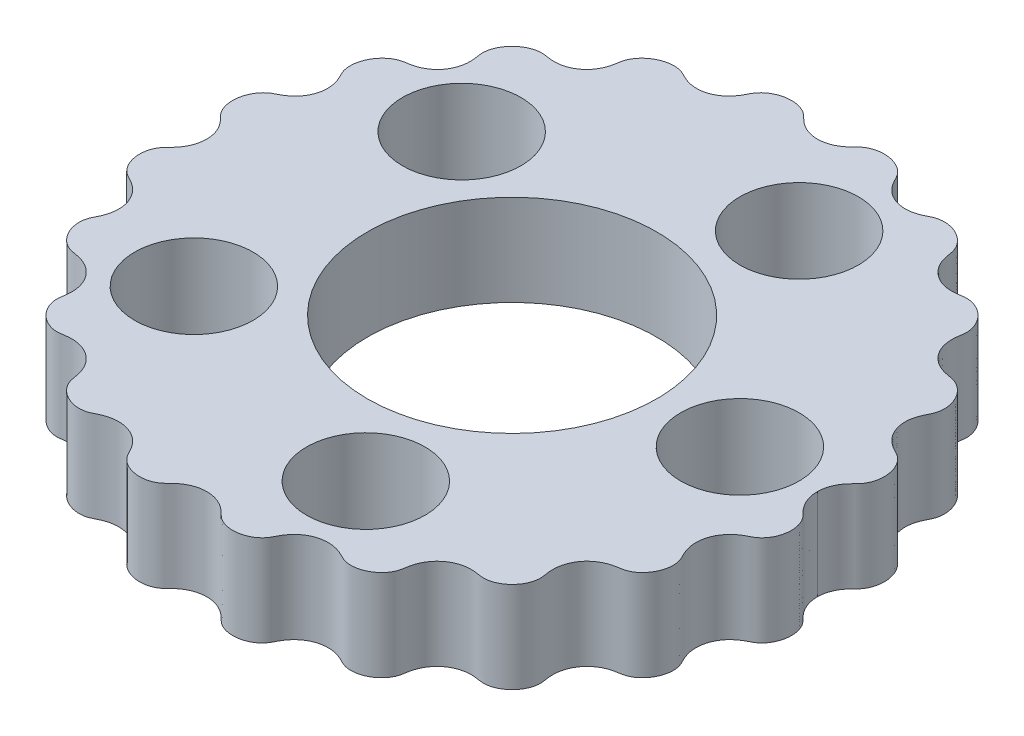
SolidWorks part; units mm, degrees
ref_plane "Front Plane" through (0, 0, 0) normal (0, 0, 1) x (1, 0, 0)
ref_plane "Top Plane" through (0, 0, 0) normal (0, 1, 0) x (1, 0, 0)
ref_plane "Right Plane" through (0, 0, 0) normal (1, 0, 0) x (0, 0, -1)
sketch "MAIN" plane through (0, 0, 0) normal (0, 1, 0) x (1, 0, 0)
  line L0 (-20.1, 0) -> (20.1, 0) construction
  line L1 (0, 0) -> (-0.8, 0)
  line L4 (0, -20.1) -> (0, 20.1) construction
  line L5 (-0.8, -20.2489) -> (-0.8, 20.2572) construction
  circle A22 centre (0, 0) radius 15
  circle A23 centre (15, 0) radius 3.9
  circle A24 centre (4.6353, -14.2658) radius 3.9
  circle A25 centre (-12.1353, -8.8168) radius 3.9
  circle A26 centre (-12.1353, 8.8168) radius 3.9
  circle A27 centre (4.6353, 14.2658) radius 3.9
  circle A29 centre (0, 0) radius 9.525
  spline S0 degree 4 poles (20.5886, 4.7068) (20.68, 4.6551) (20.8532, 4.5348) (21.1393, 4.2364) (21.3748, 3.7649) (21.4816, 3.2447) (21.4517, 2.7569) (21.3623, 2.4139) (21.2306, 2.1338) (21.0766, 1.9171) (20.8954, 1.7433) (20.7304, 1.5739) (20.553, 1.3627) (20.4068, 1.1453) (20.2874, 0.911) (20.1977, 0.6657) (20.1512, 0.4864) (20.1234, 0.3358) (20.1091, 0.21) (20.1026, 0.1123) (20.0996, 0.0252) (20.0999, -0.045) (20.1041, -0.1445) (20.1129, -0.2489) (20.1295, -0.3715) (20.1582, -0.5159) (20.2042, -0.6849) (20.2735, -0.8706) (20.3588, -1.0503) (20.459, -1.2218) (20.5666, -1.3754) (20.6778, -1.5121) (20.7891, -1.634) (20.8973, -1.7433) (21.0065, -1.8517) (21.1088, -1.9667) (21.2202, -2.1239) (21.3466, -2.3693) (21.4488, -2.7149) (21.4796, -3.1509) (21.4067, -3.6189) (21.2535, -4.0101) (21.0548, -4.3168) (20.8346, -4.5468) (20.6123, -4.7043) (20.3253, -4.8398) (20.0085, -5.0187) (19.6843, -5.2734) (19.3864, -5.6226) (19.1654, -6.0238) (19.0313, -6.4606) (18.9938, -6.8578) (19.019, -7.1969) (19.0763, -7.4737) (19.1428, -7.6897) (19.2312, -7.9077) (19.34, -8.1256) (19.4583, -8.3497) (19.5343, -8.602) (19.5712, -8.9102) (19.5475, -9.2683) (19.4413, -9.6634) (19.2307, -10.0711) (18.9626, -10.3939) (18.6946, -10.6074) (18.4633, -10.7327) (18.291, -10.7987) (18.1484, -10.8366) (18.0032, -10.862) (17.8576, -10.8843) (17.6411, -10.9233) (17.3574, -10.9968) (17.0179, -11.137) (16.6499, -11.3793) (16.3344, -11.6905) (16.085, -12.0601) (15.9134, -12.4744) (15.8373, -12.8617) (15.8261, -13.1985) (15.849, -13.4869) (15.8867, -13.7254) (15.9272, -13.9735) (15.9178, -14.2345) (15.8554, -14.5357) (15.7209, -14.8652) (15.4941, -15.2104) (15.1574, -15.5384) (14.7814, -15.7682) (14.4318, -15.8866) (14.1468, -15.9236) (13.9404, -15.918) (13.777, -15.8957) (13.5739, -15.8619) (13.3114, -15.8302) (12.9878, -15.8261) (12.6091, -15.8813) (12.2295, -16.0072) (11.877, -16.1993) (11.5634, -16.4525) (11.2997, -16.7592) (11.0942, -17.1092) (10.963, -17.4616) (10.8972, -17.764) (10.8626, -18.0051) (10.8228, -18.2154) (10.7561, -18.4196) (10.6183, -18.6831) (10.379, -18.9781) (10.0502, -19.2452) (9.6329, -19.4535) (9.2235, -19.5558) (8.8836, -19.5696) (8.6248, -19.5345) (8.4481, -19.4868) (8.3117, -19.4338) (8.1804, -19.3695) (8.0505, -19.3025) (7.8489, -19.2051) (7.5676, -19.0948) (7.1959, -19.0078) (6.7361, -18.9938) (6.2861, -19.0732) (5.8648, -19.241) (5.4886, -19.4879) (5.2101, -19.7619) (5.0117, -20.0304) (4.884, -20.2493) (4.8047, -20.4037) (4.7227, -20.5647) (4.6271, -20.7269) (4.4866, -20.8967) (4.2614, -21.0946) (3.9625, -21.275) (3.5833, -21.4148) (3.129, -21.4789) (2.7059, -21.4461) (2.3697, -21.3462) (2.1288, -21.223) (1.9722, -21.1131) (1.8575, -21.0121) (1.7229, -20.8767) (1.5347, -20.6912) (1.271, -20.4785) (0.9112, -20.275) (0.4846, -20.1344) (0.0431, -20.0821) (-0.3958, -20.1176) (-0.8148, -20.2365) (-1.152, -20.4058) (-1.4146, -20.5926) (-1.6227, -20.7757) (-1.7854, -20.9409) (-1.9581, -21.1102) (-2.1683, -21.2484) (-2.4378, -21.3695) (-2.7687, -21.4523) (-3.1582, -21.4754) (-3.5925, -21.4114) (-3.9625, -21.275) (-4.2614, -21.0946) (-4.4866, -20.8967) (-4.6271, -20.7269) (-4.7227, -20.5647) (-4.8047, -20.4037) (-4.884, -20.2493) (-5.0117, -20.0304) (-5.2101, -19.7619) (-5.4886, -19.4879) (-5.8648, -19.241) (-6.2861, -19.0732) (-6.7361, -18.9938) (-7.1959, -19.0078) (-7.5676, -19.0948) (-7.8489, -19.2051) (-8.0505, -19.3025) (-8.1804, -19.3695) (-8.3117, -19.4338) (-8.4481, -19.4868) (-8.6248, -19.5345) (-8.8836, -19.5696) (-9.2235, -19.5558) (-9.6329, -19.4535) (-10.0502, -19.2452) (-10.379, -18.9781) (-10.6183, -18.6831) (-10.7561, -18.4196) (-10.8228, -18.2154) (-10.8561, -18.0402) (-10.8777, -17.8992) (-10.9125, -17.6942) (-10.9754, -17.428) (-11.0942, -17.1093) (-11.2996, -16.7592) (-11.5634, -16.4525) (-11.877, -16.1993) (-12.2295, -16.0072) (-12.6091, -15.8813) (-12.9878, -15.8261) (-13.3114, -15.8302) (-13.5739, -15.8619) (-13.777, -15.8957) (-13.9404, -15.918) (-14.1468, -15.9236) (-14.4318, -15.8866) (-14.7814, -15.7682) (-15.1574, -15.5384) (-15.4941, -15.2104) (-15.7209, -14.8652) (-15.8554, -14.5357) (-15.9178, -14.2345) (-15.9272, -13.9735) (-15.8867, -13.7254) (-15.849, -13.4869) (-15.8261, -13.1985) (-15.8373, -12.8617) (-15.9134, -12.4744) (-16.085, -12.0601) (-16.3344, -11.6905) (-16.6499, -11.3793) (-17.0179, -11.137) (-17.3574, -10.9968) (-17.6411, -10.9233) (-17.8576, -10.8843) (-18.0032, -10.862) (-18.1484, -10.8366) (-18.291, -10.7987) (-18.4633, -10.7327) (-18.6946, -10.6074) (-18.9626, -10.3939) (-19.2307, -10.0711) (-19.4413, -9.6634) (-19.5475, -9.2683) (-19.5712, -8.9102) (-19.5343, -8.602) (-19.4583, -8.3497) (-19.34, -8.1256) (-19.2312, -7.9077) (-19.1215, -7.6374) (-19.0312, -7.3099) (-18.9886, -6.9144) (-19.0312, -6.4607) (-19.1654, -6.0238) (-19.3864, -5.6226) (-19.6843, -5.2734) (-20.0085, -5.0187) (-20.3253, -4.8398) (-20.6123, -4.7043) (-20.8346, -4.5468) (-21.0548, -4.3168) (-21.2535, -4.0101) (-21.4067, -3.6189) (-21.4796, -3.1509) (-21.4488, -2.7149) (-21.3466, -2.3693) (-21.2202, -2.1239) (-21.1088, -1.9667) (-21.0065, -1.8517) (-20.8973, -1.7433) (-20.7891, -1.634) (-20.6778, -1.5121) (-20.5666, -1.3754) (-20.459, -1.2218) (-20.3588, -1.0503) (-20.2735, -0.8706) (-20.2042, -0.6849) (-20.1582, -0.5159) (-20.1295, -0.3715) (-20.1129, -0.2489) (-20.1041, -0.1442) (-20.099, -0.0256) (-20.0999, 0.0597) (-20.107, 0.1917) (-20.1234, 0.3359) (-20.1512, 0.4864) (-20.1977, 0.6656) (-20.2874, 0.9112) (-20.4306, 1.1918) (-20.6222, 1.4599) (-20.8576, 1.7072) (-21.0766, 1.917) (-21.2306, 2.1338) (-21.3623, 2.4139) (-21.4517, 2.7569) (-21.4816, 3.2446) (-21.3748, 3.7649) (-21.1393, 4.2364) (-20.8532, 4.5348) (-20.68, 4.6551) (-20.5886, 4.7068) knots 0 0 0 0 0 0.004854 0.009708 0.018897 0.023991 0.029085 0.03214 0.035194 0.038248 0.041303 0.043723 0.046143 0.050984 0.053404 0.055825 0.058245 0.059455 0.060665 0.061539 0.062412 0.06356 0.064708 0.065855 0.067003 0.069298 0.071593 0.073888 0.076184 0.078479 0.080774 0.082553 0.084332 0.086111 0.08789 0.089668 0.091447 0.095005 0.100606 0.106208 0.111478 0.116748 0.119878 0.123007 0.126137 0.129267 0.13454 0.139813 0.145086 0.150359 0.155581 0.160804 0.163415 0.166026 0.168637 0.171249 0.174275 0.177302 0.180329 0.183356 0.188577 0.193798 0.19911 0.204423 0.207831 0.209535 0.211238 0.212942 0.214646 0.21635 0.218053 0.223116 0.228179 0.233242 0.238305 0.243486 0.248667 0.253849 0.25644 0.25903 0.262031 0.265031 0.268031 0.271032 0.27621 0.281388 0.286995 0.292602 0.296412 0.298318 0.300223 0.302128 0.304034 0.307844 0.312446 0.317047 0.321648 0.32625 0.330919 0.335589 0.340258 0.344928 0.348227 0.349876 0.351526 0.354825 0.358123 0.363551 0.368978 0.374256 0.379533 0.382914 0.384604 0.386294 0.387984 0.389675 0.391365 0.393055 0.39834 0.403624 0.408909 0.414194 0.419326 0.424458 0.429589 0.432155 0.434721 0.43617 0.437618 0.440515 0.443412 0.44631 0.451439 0.456568 0.46197 0.467372 0.470904 0.47267 0.474436 0.476202 0.477968 0.4815 0.486659 0.491818 0.496977 0.502136 0.507093 0.51205 0.517007 0.519485 0.521964 0.524855 0.527745 0.530636 0.533527 0.538479 0.543432 0.548561 0.55369 0.556588 0.559485 0.562382 0.56383 0.565279 0.567845 0.570411 0.575542 0.580674 0.585806 0.591091 0.596376 0.60166 0.606945 0.608635 0.610325 0.612016 0.613706 0.615396 0.617086 0.620467 0.625744 0.631022 0.636449 0.641877 0.645175 0.648474 0.650124 0.651773 0.653423 0.655072 0.659742 0.664411 0.669081 0.67375 0.678352 0.682953 0.687554 0.692156 0.695966 0.697872 0.699777 0.701682 0.703588 0.707398 0.713005 0.718612 0.72379 0.728968 0.731969 0.734969 0.737969 0.74097 0.74356 0.746151 0.751333 0.756514 0.761695 0.766758 0.771821 0.776884 0.781947 0.78365 0.785354 0.787058 0.788762 0.790465 0.792169 0.795577 0.80089 0.806202 0.811423 0.816644 0.819671 0.822698 0.825725 0.828751 0.831363 0.833974 0.839196 0.844419 0.849641 0.854914 0.860187 0.86546 0.870733 0.873863 0.876993 0.880122 0.883252 0.888522 0.893792 0.899394 0.904995 0.908553 0.910332 0.91211 0.913889 0.915668 0.917447 0.919226 0.921521 0.923816 0.926112 0.928407 0.930702 0.932997 0.934145 0.935292 0.93644 0.937588 0.939335 0.940545 0.941755 0.944175 0.946596 0.949016 0.953857 0.958697 0.961752 0.964806 0.96786 0.970915 0.976009 0.981103 0.990292 0.995146 1 1 1 1 1 construction
  spline S1 degree 4 poles (20.1, 0) (20.1, -0.0217) (20.1007, -0.0652) (20.1041, -0.1445) (20.1129, -0.2489) (20.1295, -0.3715) (20.1582, -0.5159) (20.2042, -0.6849) (20.2735, -0.8706) (20.3588, -1.0503) (20.459, -1.2218) (20.5666, -1.3754) (20.6778, -1.5121) (20.7891, -1.634) (20.8973, -1.7433) (21.0065, -1.8517) (21.1088, -1.9667) (21.2202, -2.1239) (21.3466, -2.3693) (21.4488, -2.7149) (21.4796, -3.1509) (21.4067, -3.6189) (21.2535, -4.0101) (21.0548, -4.3168) (20.8346, -4.5468) (20.6123, -4.7043) (20.3253, -4.8398) (20.0085, -5.0187) (19.6843, -5.2734) (19.3864, -5.6226) (19.1654, -6.0238) (19.0313, -6.4606) (18.9938, -6.8578) (19.019, -7.1969) (19.0763, -7.4737) (19.1428, -7.6897) (19.2312, -7.9077) (19.34, -8.1256) (19.4583, -8.3497) (19.5343, -8.602) (19.5712, -8.9102) (19.5475, -9.2683) (19.4413, -9.6634) (19.2307, -10.0711) (18.9626, -10.3939) (18.6946, -10.6074) (18.4633, -10.7327) (18.291, -10.7987) (18.1484, -10.8366) (18.0032, -10.862) (17.8576, -10.8843) (17.6411, -10.9233) (17.3574, -10.9968) (17.0179, -11.137) (16.6499, -11.3793) (16.3344, -11.6905) (16.085, -12.0601) (15.9134, -12.4744) (15.8373, -12.8617) (15.8261, -13.1985) (15.849, -13.4869) (15.8867, -13.7254) (15.9272, -13.9735) (15.9178, -14.2345) (15.8554, -14.5357) (15.7209, -14.8652) (15.4941, -15.2104) (15.1574, -15.5384) (14.7814, -15.7682) (14.4318, -15.8866) (14.1468, -15.9236) (13.9404, -15.918) (13.777, -15.8957) (13.5739, -15.8619) (13.3114, -15.8302) (12.9878, -15.8261) (12.6091, -15.8813) (12.2295, -16.0072) (11.877, -16.1993) (11.5634, -16.4525) (11.2997, -16.7592) (11.0942, -17.1092) (10.963, -17.4616) (10.8972, -17.764) (10.8626, -18.0051) (10.8228, -18.2154) (10.7561, -18.4196) (10.6183, -18.6831) (10.379, -18.9781) (10.0502, -19.2452) (9.6329, -19.4535) (9.2235, -19.5558) (8.8836, -19.5696) (8.6248, -19.5345) (8.4481, -19.4868) (8.3117, -19.4338) (8.1804, -19.3695) (8.0505, -19.3025) (7.8489, -19.2051) (7.5676, -19.0948) (7.1959, -19.0078) (6.7361, -18.9938) (6.2861, -19.0732) (5.8648, -19.241) (5.4886, -19.4879) (5.2101, -19.7619) (5.0117, -20.0304) (4.884, -20.2493) (4.8047, -20.4037) (4.7227, -20.5647) (4.6271, -20.7269) (4.4866, -20.8967) (4.2614, -21.0946) (3.9625, -21.275) (3.5833, -21.4148) (3.129, -21.4789) (2.7059, -21.4461) (2.3697, -21.3462) (2.1288, -21.223) (1.9722, -21.1131) (1.8575, -21.0121) (1.7229, -20.8767) (1.5347, -20.6912) (1.271, -20.4785) (0.9112, -20.275) (0.4846, -20.1344) (0.0431, -20.0821) (-0.3958, -20.1176) (-0.8148, -20.2365) (-1.152, -20.4058) (-1.4146, -20.5926) (-1.6227, -20.7757) (-1.7854, -20.9409) (-1.9581, -21.1102) (-2.1683, -21.2484) (-2.4378, -21.3695) (-2.7687, -21.4523) (-3.1582, -21.4754) (-3.5925, -21.4114) (-3.9625, -21.275) (-4.2614, -21.0946) (-4.4866, -20.8967) (-4.6271, -20.7269) (-4.7227, -20.5647) (-4.8047, -20.4037) (-4.884, -20.2493) (-5.0117, -20.0304) (-5.2101, -19.7619) (-5.4886, -19.4879) (-5.8648, -19.241) (-6.2861, -19.0732) (-6.7361, -18.9938) (-7.1959, -19.0078) (-7.5676, -19.0948) (-7.8489, -19.2051) (-8.0505, -19.3025) (-8.1804, -19.3695) (-8.3117, -19.4338) (-8.4481, -19.4868) (-8.6248, -19.5345) (-8.8836, -19.5696) (-9.2235, -19.5558) (-9.6329, -19.4535) (-10.0502, -19.2452) (-10.379, -18.9781) (-10.6183, -18.6831) (-10.7561, -18.4196) (-10.8228, -18.2154) (-10.8561, -18.0402) (-10.8777, -17.8992) (-10.9125, -17.6942) (-10.9754, -17.428) (-11.0942, -17.1093) (-11.2996, -16.7592) (-11.5634, -16.4525) (-11.877, -16.1993) (-12.2295, -16.0072) (-12.6091, -15.8813) (-12.9878, -15.8261) (-13.3114, -15.8302) (-13.5739, -15.8619) (-13.777, -15.8957) (-13.9404, -15.918) (-14.1468, -15.9236) (-14.4318, -15.8866) (-14.7814, -15.7682) (-15.1574, -15.5384) (-15.4941, -15.2104) (-15.7209, -14.8652) (-15.8554, -14.5357) (-15.9178, -14.2345) (-15.9272, -13.9735) (-15.8867, -13.7254) (-15.849, -13.4869) (-15.8261, -13.1985) (-15.8373, -12.8617) (-15.9134, -12.4744) (-16.085, -12.0601) (-16.3344, -11.6905) (-16.6499, -11.3793) (-17.0179, -11.137) (-17.3574, -10.9968) (-17.6411, -10.9233) (-17.8576, -10.8843) (-18.0032, -10.862) (-18.1484, -10.8366) (-18.291, -10.7987) (-18.4633, -10.7327) (-18.6946, -10.6074) (-18.9626, -10.3939) (-19.2307, -10.0711) (-19.4413, -9.6634) (-19.5475, -9.2683) (-19.5712, -8.9102) (-19.5343, -8.602) (-19.4583, -8.3497) (-19.34, -8.1256) (-19.2312, -7.9077) (-19.1215, -7.6374) (-19.0312, -7.3099) (-18.9886, -6.9144) (-19.0312, -6.4607) (-19.1654, -6.0238) (-19.3864, -5.6226) (-19.6843, -5.2734) (-20.0085, -5.0187) (-20.3253, -4.8398) (-20.6123, -4.7043) (-20.8346, -4.5468) (-21.0548, -4.3168) (-21.2535, -4.0101) (-21.4067, -3.6189) (-21.4796, -3.1509) (-21.4488, -2.7149) (-21.3466, -2.3693) (-21.2202, -2.1239) (-21.1088, -1.9667) (-21.0065, -1.8517) (-20.8973, -1.7433) (-20.7891, -1.634) (-20.6778, -1.5121) (-20.5666, -1.3754) (-20.459, -1.2218) (-20.3588, -1.0503) (-20.2735, -0.8706) (-20.2042, -0.6849) (-20.1582, -0.5159) (-20.1295, -0.3715) (-20.1129, -0.2489) (-20.1041, -0.1442) (-20.1007, -0.0655) (-20.1, -0.0217) (-20.1, 0) knots 0.062412 0.062412 0.062412 0.062412 0.062412 0.06356 0.064708 0.065855 0.067003 0.069298 0.071593 0.073888 0.076184 0.078479 0.080774 0.082553 0.084332 0.086111 0.08789 0.089668 0.091447 0.095005 0.100606 0.106208 0.111478 0.116748 0.119878 0.123007 0.126137 0.129267 0.13454 0.139813 0.145086 0.150359 0.155581 0.160804 0.163415 0.166026 0.168637 0.171249 0.174275 0.177302 0.180329 0.183356 0.188577 0.193798 0.19911 0.204423 0.207831 0.209535 0.211238 0.212942 0.214646 0.21635 0.218053 0.223116 0.228179 0.233242 0.238305 0.243486 0.248667 0.253849 0.25644 0.25903 0.262031 0.265031 0.268031 0.271032 0.27621 0.281388 0.286995 0.292602 0.296412 0.298318 0.300223 0.302128 0.304034 0.307844 0.312446 0.317047 0.321648 0.32625 0.330919 0.335589 0.340258 0.344928 0.348227 0.349876 0.351526 0.354825 0.358123 0.363551 0.368978 0.374256 0.379533 0.382914 0.384604 0.386294 0.387984 0.389675 0.391365 0.393055 0.39834 0.403624 0.408909 0.414194 0.419326 0.424458 0.429589 0.432155 0.434721 0.43617 0.437618 0.440515 0.443412 0.44631 0.451439 0.456568 0.46197 0.467372 0.470904 0.47267 0.474436 0.476202 0.477968 0.4815 0.486659 0.491818 0.496977 0.502136 0.507093 0.51205 0.517007 0.519485 0.521964 0.524855 0.527745 0.530636 0.533527 0.538479 0.543432 0.548561 0.55369 0.556588 0.559485 0.562382 0.56383 0.565279 0.567845 0.570411 0.575542 0.580674 0.585806 0.591091 0.596376 0.60166 0.606945 0.608635 0.610325 0.612016 0.613706 0.615396 0.617086 0.620467 0.625744 0.631022 0.636449 0.641877 0.645175 0.648474 0.650124 0.651773 0.653423 0.655072 0.659742 0.664411 0.669081 0.67375 0.678352 0.682953 0.687554 0.692156 0.695966 0.697872 0.699777 0.701682 0.703588 0.707398 0.713005 0.718612 0.72379 0.728968 0.731969 0.734969 0.737969 0.74097 0.74356 0.746151 0.751333 0.756514 0.761695 0.766758 0.771821 0.776884 0.781947 0.78365 0.785354 0.787058 0.788762 0.790465 0.792169 0.795577 0.80089 0.806202 0.811423 0.816644 0.819671 0.822698 0.825725 0.828751 0.831363 0.833974 0.839196 0.844419 0.849641 0.854914 0.860187 0.86546 0.870733 0.873863 0.876993 0.880122 0.883252 0.888522 0.893792 0.899394 0.904995 0.908553 0.910332 0.91211 0.913889 0.915668 0.917447 0.919226 0.921521 0.923816 0.926112 0.928407 0.930702 0.932997 0.934145 0.935292 0.93644 0.937588 0.937588 0.937588 0.937588 0.937588
  spline S2 degree 4 poles (20.1, 0) (20.1, 0.016) (20.1004, 0.0483) (20.103, 0.1222) (20.112, 0.2418) (20.1299, 0.3658) (20.1605, 0.5103) (20.2009, 0.6519) (20.2511, 0.7903) (20.3105, 0.925) (20.405, 1.1055) (20.5226, 1.2843) (20.6637, 1.4579) (20.8251, 1.6262) (20.9585, 1.7565) (21.084, 1.8949) (21.1907, 2.0485) (21.3222, 2.2956) (21.4364, 2.6526) (21.4803, 3.1177) (21.4039, 3.6005) (21.2554, 3.9885) (21.0881, 4.2662) (20.9406, 4.4515) (20.7839, 4.6031) (20.6242, 4.7228) (20.4498, 4.8192) (20.2714, 4.9072) (20.0538, 5.0278) (19.7727, 5.2201) (19.4603, 5.5221) (19.1704, 5.9791) (19.0001, 6.551) (18.9968, 7.0935) (19.1004, 7.5221) (19.226, 7.825) (19.3231, 8.0197) (19.4032, 8.1742) (19.4892, 8.3744) (19.5665, 8.6825) (19.5779, 9.1011) (19.4647, 9.6109) (19.2312, 10.0617) (18.9516, 10.3963) (18.6873, 10.6122) (18.4786, 10.7388) (18.2767, 10.8266) (18.088, 10.8805) (17.8946, 10.9117) (17.7013, 10.9419) (17.5098, 10.9831) (17.3219, 11.0382) (17.0549, 11.141) (16.7249, 11.3247) (16.3639, 11.6361) (16.0441, 12.1125) (15.8775, 12.6141) (15.841, 13.046) (15.8658, 13.3784) (15.9011, 13.611) (15.9319, 13.7968) (15.9482, 14.0321) (15.9148, 14.3537) (15.7871, 14.7447) (15.5207, 15.1776) (15.173, 15.5163) (14.8159, 15.7409) (14.503, 15.8642) (14.2676, 15.9213) (14.0488, 15.9441) (13.8511, 15.9387) (13.6559, 15.909) (13.4613, 15.8774) (13.265, 15.8568) (13.0677, 15.8506) (12.7762, 15.8657) (12.3956, 15.941) (11.9386, 16.1371) (11.4706, 16.5199) (11.1629, 16.9705) (11.0089, 17.3828) (10.9417, 17.7007) (10.9094, 17.9106) (10.8813, 18.0783) (10.8259, 18.2838) (10.7008, 18.5665) (10.4632, 18.8965) (10.1065, 19.2033) (9.6723, 19.4296) (9.2327, 19.5511) (8.8627, 19.5763) (8.5739, 19.5408) (8.3713, 19.483) (8.2335, 19.4293) (8.1088, 19.3698) (7.9719, 19.2984) (7.8178, 19.2242) (7.6203, 19.1423) (7.3752, 19.0655) (7.0593, 19.0086) (6.6743, 19.0056) (6.2349, 19.0853) (5.7672, 19.2865) (5.3804, 19.5853) (5.1146, 19.9125) (4.9536, 20.1837) (4.8383, 20.4088) (4.7236, 20.6354) (4.5008, 20.9158) (4.1338, 21.1948) (3.6506, 21.4015) (3.1414, 21.4742) (2.7011, 21.4391) (2.3677, 21.3457) (2.1404, 21.2452) (1.9708, 21.1395) (1.8527, 21.0456) (1.7606, 20.9601) (1.6892, 20.8895) (1.6182, 20.8184) (1.546, 20.7486) (1.4535, 20.6637) (1.3379, 20.5669) (1.1957, 20.4632) (0.9444, 20.3112) (0.5869, 20.1608) (0.0974, 20.0677) (-0.5067, 20.1237) (-1.0106, 20.3249) (-1.3647, 20.5768) (-1.5935, 20.7925) (-1.7318, 20.9329) (-1.8462, 21.0415) (-2.0019, 21.1628) (-2.2547, 21.308) (-2.6214, 21.4316) (-3.112, 21.4794) (-3.6642, 21.3957) (-4.1338, 21.1948) (-4.5008, 20.9158) (-4.7236, 20.6354) (-4.8383, 20.4088) (-4.9536, 20.1837) (-5.1146, 19.9125) (-5.3804, 19.5853) (-5.7672, 19.2865) (-6.2349, 19.0853) (-6.6743, 19.0056) (-7.0593, 19.0086) (-7.3752, 19.0655) (-7.6203, 19.1423) (-7.8178, 19.2242) (-7.9719, 19.2984) (-8.1088, 19.3698) (-8.2335, 19.4293) (-8.3713, 19.483) (-8.5739, 19.5408) (-8.8627, 19.5763) (-9.2327, 19.5511) (-9.6723, 19.4296) (-10.1065, 19.2033) (-10.4632, 18.8965) (-10.7008, 18.5665) (-10.8259, 18.2838) (-10.8813, 18.0783) (-10.9094, 17.9106) (-10.9417, 17.7007) (-11.0089, 17.3828) (-11.1629, 16.9705) (-11.4705, 16.5199) (-11.9386, 16.1371) (-12.4415, 15.9213) (-12.8743, 15.8493) (-13.2159, 15.8516) (-13.4613, 15.8774) (-13.6559, 15.909) (-13.8511, 15.9387) (-14.0488, 15.9441) (-14.2676, 15.9213) (-14.503, 15.8642) (-14.8159, 15.7409) (-15.173, 15.5163) (-15.5207, 15.1776) (-15.7871, 14.7447) (-15.9148, 14.3537) (-15.9482, 14.0321) (-15.9319, 13.7968) (-15.9011, 13.611) (-15.8658, 13.3784) (-15.841, 13.046) (-15.8775, 12.6141) (-16.0441, 12.1125) (-16.3639, 11.6361) (-16.7249, 11.3247) (-17.0549, 11.141) (-17.3219, 11.0382) (-17.5098, 10.9831) (-17.7013, 10.9419) (-17.8946, 10.9117) (-18.088, 10.8805) (-18.2767, 10.8266) (-18.4786, 10.7388) (-18.6873, 10.6122) (-18.9516, 10.3963) (-19.2312, 10.0617) (-19.4647, 9.6109) (-19.5779, 9.1011) (-19.5665, 8.6825) (-19.4892, 8.3744) (-19.4032, 8.1742) (-19.3231, 8.0197) (-19.226, 7.825) (-19.1004, 7.5221) (-18.9968, 7.0935) (-19.0001, 6.551) (-19.1704, 5.9791) (-19.4603, 5.5221) (-19.7727, 5.2201) (-20.0538, 5.0278) (-20.2714, 4.9072) (-20.4498, 4.8192) (-20.6242, 4.7228) (-20.7839, 4.6031) (-20.9406, 4.4515) (-21.0881, 4.2662) (-21.2554, 3.9885) (-21.4039, 3.6005) (-21.4803, 3.1177) (-21.4364, 2.6526) (-21.3222, 2.2956) (-21.1907, 2.0485) (-21.084, 1.8949) (-20.9585, 1.7565) (-20.8251, 1.6262) (-20.6637, 1.4579) (-20.5226, 1.2843) (-20.405, 1.1055) (-20.3105, 0.925) (-20.2511, 0.7903) (-20.2009, 0.6519) (-20.1605, 0.5103) (-20.1299, 0.3658) (-20.112, 0.2419) (-20.103, 0.1218) (-20.1004, 0.0485) (-20.1, 0.016) (-20.1, 0) knots 0.063609 0.063609 0.063609 0.063609 0.063609 0.064458 0.065307 0.067005 0.068703 0.070402 0.0721 0.073798 0.075496 0.077194 0.0815 0.083653 0.085806 0.087958 0.090111 0.092264 0.094417 0.100851 0.107286 0.113599 0.116755 0.119912 0.122208 0.124504 0.1268 0.129096 0.131392 0.133688 0.13828 0.144787 0.151294 0.158382 0.16547 0.169487 0.171496 0.173504 0.175513 0.177521 0.181538 0.188089 0.19464 0.201359 0.204718 0.208078 0.210337 0.212596 0.214854 0.217113 0.219372 0.221631 0.22389 0.226149 0.232563 0.238978 0.24565 0.252321 0.256667 0.25884 0.261013 0.263186 0.265358 0.269704 0.275849 0.281993 0.288591 0.29189 0.295189 0.297466 0.299742 0.302018 0.304295 0.306571 0.308848 0.311124 0.3134 0.320031 0.326662 0.333804 0.340946 0.344869 0.34683 0.348792 0.350753 0.352715 0.356638 0.362993 0.369347 0.374207 0.379066 0.383919 0.386345 0.387558 0.388771 0.390744 0.392717 0.39469 0.396663 0.400609 0.404555 0.40945 0.414345 0.42109 0.427836 0.431732 0.433681 0.435629 0.439525 0.443422 0.450062 0.456701 0.463502 0.466903 0.470303 0.472622 0.474941 0.476101 0.47726 0.47842 0.479579 0.480739 0.481898 0.484217 0.486536 0.488855 0.49544 0.502026 0.50926 0.516494 0.520133 0.521952 0.523772 0.525591 0.527411 0.53105 0.537174 0.543299 0.549938 0.556578 0.560475 0.564371 0.566319 0.568268 0.572164 0.57891 0.585655 0.59055 0.595445 0.599391 0.603337 0.60531 0.607283 0.609256 0.611229 0.612442 0.613655 0.616081 0.620934 0.625793 0.630653 0.637007 0.643362 0.647285 0.649247 0.651208 0.65317 0.655131 0.659054 0.666196 0.673338 0.679969 0.6866 0.691152 0.693429 0.695705 0.697982 0.700258 0.702534 0.704811 0.70811 0.711409 0.718007 0.724151 0.730296 0.734642 0.736814 0.738987 0.74116 0.743333 0.747679 0.75435 0.761022 0.767437 0.773851 0.77611 0.778369 0.780628 0.782887 0.785146 0.787404 0.789663 0.791922 0.795282 0.798641 0.80536 0.811911 0.818462 0.822479 0.824487 0.826496 0.828504 0.830513 0.83453 0.841618 0.848706 0.855213 0.86172 0.866312 0.868608 0.870904 0.8732 0.875496 0.877792 0.880088 0.883245 0.886401 0.892714 0.899149 0.905583 0.907736 0.909889 0.912042 0.914194 0.916347 0.9185 0.922806 0.924504 0.926202 0.9279 0.929598 0.931297 0.932995 0.934693 0.935542 0.936391 0.936391 0.936391 0.936391 0.936391
  point P67 (0, 0)
  dimension "D1" = 19.05
  dimension "D4" = 30
  dimension "D5" = 7.8
  dimension "D6" = 5
extrude "Boss-Extrude1" add sketch "MAIN" along normal blind 6 from offset 1 contours S1 S2 A27 A22 A23 A24 A25 A26 | A27 A22 A26 A25 A24 A23 A29 region at (10.6793, 0, 0) region at (0, 0, 19.4931)
